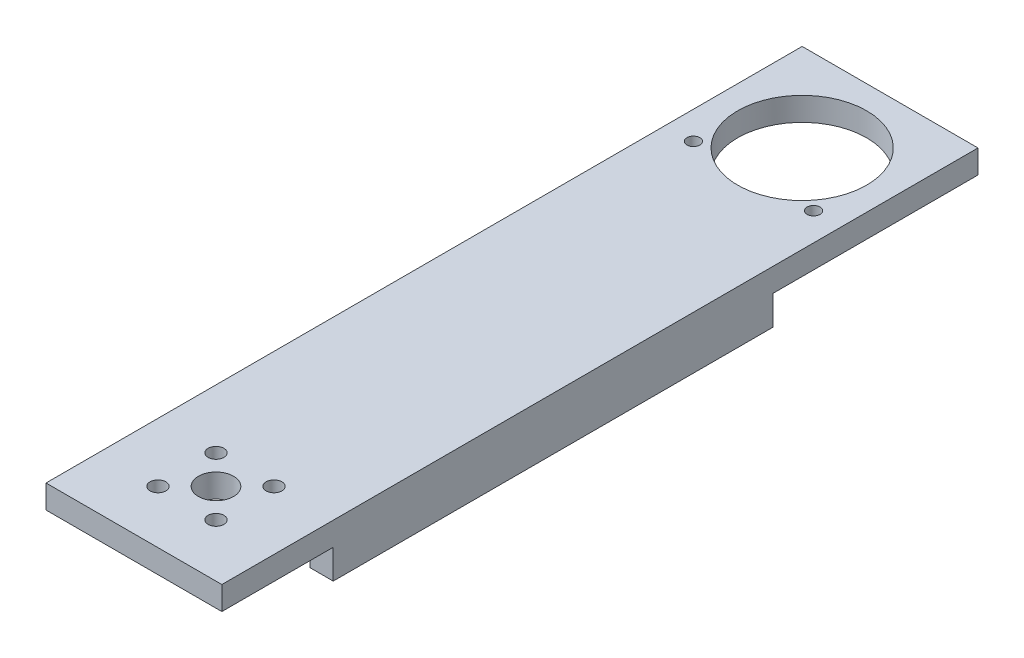
SolidWorks part; units mm, degrees
ref_plane "Front Plane" through (0, 0, 0) normal (0, 0, 1) x (1, 0, 0)
ref_plane "Top Plane" through (0, 0, 0) normal (0, 1, 0) x (1, 0, 0)
ref_plane "Right Plane" through (0, 0, 0) normal (1, 0, 0) x (0, 0, -1)
ref_plane "PZ_m115_000" through (0, 0, -115) normal (0, 0, 1) x (1, 0, 0)
sketch "S_box1" plane through (0, 0, -115) normal (0, 0, 1) x (1, 0, 0)
  line L0 (-15, -22.625) -> (15, -22.625)
  line L1 (15, -22.625) -> (15, -18.625)
  line L2 (15, -18.625) -> (-15, -18.625)
  line L3 (-15, -18.625) -> (-15, -22.625)
  dimension "P1" = 15
  dimension "P2" = 22.625
  dimension "P3" = 15
  dimension "P4" = 22.625
  dimension "P5" = 15
  dimension "P6" = 18.625
  dimension "P7" = 15
  dimension "P8" = 18.625
extrude "Boss_1" add sketch "S_box1" along normal blind 129
ref_plane "PZ_m80_000" through (0, 0, -80) normal (0, 0, 1) x (1, 0, 0)
sketch "S_box2" plane through (0, 0, -80) normal (0, 0, 1) x (1, 0, 0)
  line L0 (-15, -27.625) -> (-11, -27.625)
  line L1 (-11, -27.625) -> (-11, -22.125)
  line L2 (-11, -22.125) -> (-15, -22.125)
  line L3 (-15, -22.125) -> (-15, -27.625)
  dimension "P1" = 15
  dimension "P2" = 27.625
  dimension "P3" = 11
  dimension "P4" = 27.625
  dimension "P5" = 11
  dimension "P6" = 22.125
  dimension "P7" = 15
  dimension "P8" = 22.125
extrude "Boss_2" add sketch "S_box2" along normal blind 75
sketch "S_box3" plane through (0, 0, -80) normal (0, 0, 1) x (1, 0, 0)
  line L0 (11, -27.625) -> (15, -27.625)
  line L1 (15, -27.625) -> (15, -22.125)
  line L2 (15, -22.125) -> (11, -22.125)
  line L3 (11, -22.125) -> (11, -27.625)
  dimension "P1" = 11
  dimension "P2" = 27.625
  dimension "P3" = 15
  dimension "P4" = 27.625
  dimension "P5" = 15
  dimension "P6" = 22.125
  dimension "P7" = 11
  dimension "P8" = 22.125
extrude "Boss_3" add sketch "S_box3" along normal blind 75
ref_plane "PY_m22_725" through (0, -22.725, 0) normal (0, 1, 0) x (1, 0, 0)
sketch "S_hole4" plane through (0, -22.725, 0) normal (0, 1, 0) x (1, 0, 0)
  circle A0 centre (0, 0) radius 3
  dimension "D1_S_hole4" = 6
extrude "Hole_4" cut sketch "S_hole4" along normal blind 4.2
sketch "S_hole5" plane through (0, -22.725, 0) normal (0, 1, 0) x (1, 0, 0)
  circle A0 centre (4.9497, -4.9497) radius 1.35
  dimension "D1_S_hole5" = 2.7
  dimension "P2" = 4.9497
  dimension "P3" = 4.9497
extrude "Hole_5" cut sketch "S_hole5" along normal blind 4.2
sketch "S_hole6" plane through (0, -22.725, 0) normal (0, 1, 0) x (1, 0, 0)
  circle A0 centre (-4.9497, -4.9497) radius 1.35
  dimension "D1_S_hole6" = 2.7
  dimension "P2" = 4.9497
  dimension "P3" = 4.9497
extrude "Hole_6" cut sketch "S_hole6" along normal blind 4.2
sketch "S_hole7" plane through (0, -22.725, 0) normal (0, 1, 0) x (1, 0, 0)
  circle A0 centre (-4.9497, 4.9497) radius 1.35
  dimension "D1_S_hole7" = 2.7
  dimension "P2" = 4.9497
  dimension "P3" = 4.9497
extrude "Hole_7" cut sketch "S_hole7" along normal blind 4.2
sketch "S_hole8" plane through (0, -22.725, 0) normal (0, 1, 0) x (1, 0, 0)
  circle A0 centre (4.9497, 4.9497) radius 1.35
  dimension "D1_S_hole8" = 2.7
  dimension "P2" = 4.9497
  dimension "P3" = 4.9497
extrude "Hole_8" cut sketch "S_hole8" along normal blind 4.2
sketch "S_hole9" plane through (0, -22.725, 0) normal (0, 1, 0) x (1, 0, 0)
  circle A0 centre (0, 100) radius 11
  dimension "D1_S_hole9" = 22
  dimension "P2" = 100
extrude "Hole_9" cut sketch "S_hole9" along normal blind 4.2
sketch "S_hole10" plane through (0, -22.725, 0) normal (0, 1, 0) x (1, 0, 0)
  circle A0 centre (-10.25, 91.7) radius 1.1
  dimension "D1_S_hole10" = 2.2
  dimension "P2" = 10.25
  dimension "P3" = 91.7
extrude "Hole_10" cut sketch "S_hole10" along normal blind 4.2
sketch "S_hole11" plane through (0, -22.725, 0) normal (0, 1, 0) x (1, 0, 0)
  circle A0 centre (10.25, 91.7) radius 1.1
  dimension "D1_S_hole11" = 2.2
  dimension "P2" = 10.25
  dimension "P3" = 91.7
extrude "Hole_11" cut sketch "S_hole11" along normal blind 4.2
sketch "S_hole12" plane through (0, -22.725, 0) normal (0, 1, 0) x (1, 0, 0)
  circle A0 centre (-10.25, 67.25) radius 1.1
  dimension "D1_S_hole12" = 2.2
  dimension "P2" = 10.25
  dimension "P3" = 67.25
extrude "Hole_12" cut sketch "S_hole12" against normal blind 4.2
sketch "S_hole13" plane through (0, -22.725, 0) normal (0, 1, 0) x (1, 0, 0)
  circle A0 centre (10.25, 67.25) radius 1.1
  dimension "D1_S_hole13" = 2.2
  dimension "P2" = 10.25
  dimension "P3" = 67.25
extrude "Hole_13" cut sketch "S_hole13" against normal blind 4.2
equation "\"plate_t\" = 3"
equation "\"clearance\" = 0.4"
